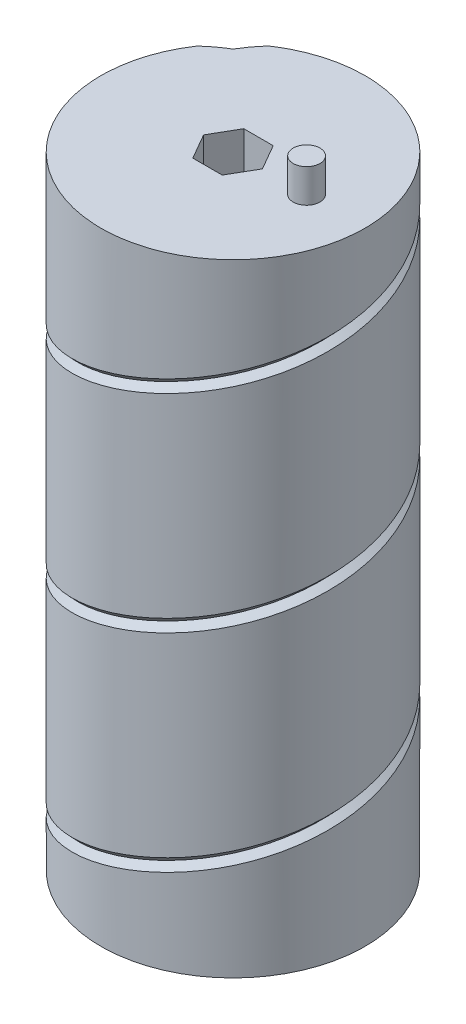
SolidWorks part; units mm, degrees
note: The reader was unsure of these and kept them because the rebuilt part matched: shared geometry of "Sketch1<2>".
ref_plane "Front Plane" through (0, 0, 0) normal (0, 0, 1) x (1, 0, 0)
ref_plane "Top Plane" through (0, 0, 0) normal (0, 1, 0) x (1, 0, 0)
ref_plane "Right Plane" through (0, 0, 0) normal (1, 0, 0) x (0, 0, -1)
sketch "Sketch1" plane through (0, 0, 0) normal (0, 1, 0) x (1, 0, 0)
  line L0 (-19.75, 0) -> (19.75, 0) construction
  circle A0 centre (0, 0) radius 19.75
  dimension "D1" = 39.5
curve "Helix - Antenna Guide" pitch 31 height 93 radius 19.75 centre (0, 0, 0) axis (0, 1, 0) start towards (0, 0, 1)
extrude "Extrude - Main Body" add sketch "Sketch1<2>" along normal blind 93
sketch "Sketch1<2>" plane through (0, 0, 0) normal (0, 1, 0) x (1, 0, 0) same geometry as "Sketch1"
ref_point "Point2"
ref_point "Point1"
ref_plane "Plane1" through (-13.9654, 0, -13.9654) normal (-0.686, 0.2424, 0.686) x (-0.7276, -0.2285, -0.6468)
sketch "Sketch15" plane through (-13.9654, 0, -13.9654) normal (-0.686, 0.2424, 0.686) x (-0.7276, -0.2285, -0.6468)
  line L4 (0, 0) -> (0.2165, 0.8934)
  line L5 (0.2165, 0.8934) -> (-0.8934, 0.2165)
  line L8 (0, 0) -> (-0.2165, -0.8934)
  line L9 (-0.2165, -0.8934) -> (-0.8934, 0.2165)
  point P7 (-0.5549, -0.3384)
  dimension "D1" = 0.65
  dimension "D2" = 90
sweep "Cut - Antenna Wire Guide" cut profiles "Sketch15" path "Helix - Antenna Guide" align with end faces yes
sketch "Sketch26" plane through (0, 93, 0) normal (0, 1, 0) x (1, 0, 0)
  point P0 (0, 0)
hole_wizard "#8 Clearance Hole1" positions "Sketch27" profile "Sketch28" hole size "#8" standard "ANSI Inch" end condition through all
sketch "Sketch27" plane through (0, 93, 0) normal (0, 1, 0) x (1, 0, 0)
  point P0 (0, 0)
sketch "Sketch28" plane through (0, 93, 0) normal (1, 0, 0) x (0, 0, 1)
  line L0 (0, 0) -> (0, 94.4693)
  line L1 (0, 94.4693) -> (2.2479, 94.4693)
  line L2 (2.2479, 94.4693) -> (2.2479, 0)
  line L5 (2.2479, 0) -> (0, 0)
  line L11 (0, -6.35) -> (0, 107.95) construction
  dimension "Thru Hole Dia." = 4.4958
  dimension "Thru Hole Depth" = 94.4693
sketch "Sketch29" plane through (0, 93, 0) normal (0, 1, 0) x (1, 0, 0)
  circle A0 centre (11, 0) radius 2
  dimension "D2" = 4
  dimension "D1" = 11
extrude "Extruded Peg" add sketch "Sketch29" along normal blind 5
sketch "Sketch30" plane through (0, 0, 0) normal (0, -1, 0) x (1, 0, 0)
  circle A4 centre (0, 0) radius 32.5
  point P0 (0, 0)
  dimension "D1" = 65
extrude "Boss-Extrude5" [suppressed] add sketch "Sketch30" along normal blind 5
sketch "Sketch34" [suppressed] plane through (0, 0, 0) normal (0, 1, 0) x (1, 0, 0)
  line L0 (0, 0) -> (0, 25) construction
  point P0 (0, 25)
  point P4 (25, 0)
  point P6 (0, -25)
  point P7 (-25, 0)
  dimension "D1" = 25
  dimension "D2" = 4
hole_wizard "#8 Clearance Hole2" [suppressed] positions "Sketch35" profile "Sketch36" hole size "#8" standard "ANSI Inch"
sketch "Sketch35" [suppressed] plane through (0, 0, 0) normal (0, 1, 0) x (1, 0, 0)
  point P0 (25, 0)
  point P3 (0, 25)
  point P6 (-25, 0)
  point P9 (0, -25)
sketch "Sketch36" plane through (25, 0, 0) normal (1, 0, 0) x (0, 0, 1)
  line L0 (0, 0) -> (0, 5)
  line L1 (0, 5) -> (2.2479, 5)
  line L2 (2.2479, 5) -> (2.2479, 0)
  line L5 (2.2479, 0) -> (0, 0)
  line L11 (0, -6.35) -> (0, 107.95) construction
  dimension "Thru Hole Dia." = 4.4958
  dimension "Thru Hole Depth" = 5
sketch "Sketch37" [suppressed] plane through (0, 0, 0) normal (0, 1, 0) x (1, 0, 0)
  line L1 (19.75, 25.8106) -> (19.75, -25.8106)
  line L3 (-19.75, 25.8106) -> (-19.75, -25.8106)
  circle A1 centre (0, 0) radius 32.5 construction
  arc A2 (19.75, 25.8106) -> (19.75, -25.8106) centre (0, 0) cw
  arc A3 (-19.75, 25.8106) -> (-19.75, -25.8106) centre (0, 0) ccw
extrude "Cut-Extrude4" [suppressed] cut sketch "Sketch37" against normal up to surface (5 mm away)
fillet "Fillet1" [suppressed] radius 10
sketch "Sketch41" [suppressed] plane through (-19.75, 0, 0) normal (-1, 0, 0) x (0, 0, 1)
  line L0 (0, 0) -> (0, 93) construction
  line L1 (19.75, 93) -> (-19.75, 93) construction
  text T0 "1" font "Century Gothic" height 10
  dimension "D1" = 4
  dimension "D2" = 40
extrude "Cut-Extrude6" [suppressed] cut sketch "Sketch41" against normal blind 3
sketch "Sketch42" plane through (0, 93, 0) normal (0, 1, 0) x (1, 0, 0)
  line L1 (-2.1997, -3.81) -> (2.1997, -3.81)
  line L2 (2.1997, -3.81) -> (4.3994, 0)
  line L3 (4.3994, 0) -> (2.1997, 3.81)
  line L4 (2.1997, 3.81) -> (-2.1997, 3.81)
  line L5 (-2.1997, 3.81) -> (-4.3994, 0)
  line L6 (-4.3994, 0) -> (-2.1997, -3.81)
  circle A0 centre (0, 0) radius 3.81 construction
  point P1 (0, 0)
  dimension "D1" = 7.62
extrude "Cut-Extrude7" cut sketch "Sketch42" against normal blind 26.67
sketch "Sketch43" plane through (0, 0, 0) normal (0, -1, 0) x (1, 0, 0)
  circle A0 centre (11, 0) radius 2.25
  point P2 (0, 0)
  dimension "D2" = 4.5
  dimension "D1" = 11
extrude "Cut-Extrude8" cut sketch "Sketch43" against normal blind 5.5
ref_plane "Plane2" through (-19.75, 93, 0) normal (-1, 0, 0) x (0, 0, 1)
sketch "Sketch44" plane through (-19.75, 93, 0) normal (-1, 0, 0) x (0, 0, 1)
  line L0 (0, -93) -> (0, 0) construction
  line L1 (19.75, 0) -> (-19.75, 0) construction
  line L2 (-19.75, -93) -> (19.75, -93) construction
  text T0 "2" font "Century Gothic" height 10
  point P4 (0, -13.2231)
  dimension "D1" = 4
  dimension "D2" = 49
extrude "Cut-Extrude9" cut sketch "Sketch44" against normal blind 5
equation "\"pegD\"=10"
equation "\"pegHoleD\"=0.5"
equation "\"pegHoleOffset\"=0.5"
